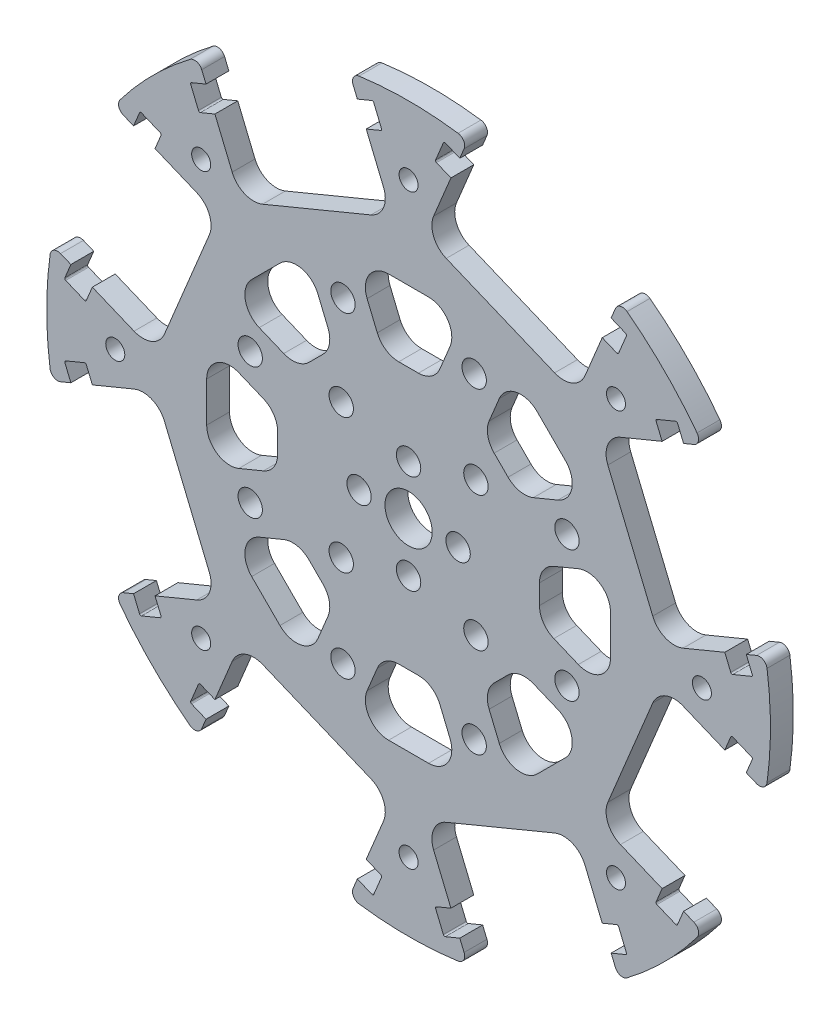
SolidWorks part; units mm, degrees
material "5052-H34"
ref_plane "正面" through (0, 0, 0) normal (0, 0, 1) x (1, 0, 0)
ref_plane "平面" through (0, 0, 0) normal (0, 1, 0) x (1, 0, 0)
ref_plane "右側面" through (0, 0, 0) normal (1, 0, 0) x (0, 0, -1)
sketch "ｽｹｯﾁ1" plane through (0, 0, 0) normal (0, 0, 1) x (1, 0, 0)
  circle A0 centre (0, 0) radius 47.5
  dimension "D1" = 95
extrude "ﾎﾞｽ - 押し出し1" add sketch "ｽｹｯﾁ1" along normal blind 3
sketch "ｽｹｯﾁ2" plane through (0, 0, 3) normal (0, 0, 1) x (1, 0, 0)
  line L0 (0, 0) -> (18.1775, 43.8843) construction
  line L1 (6.7246, 44.3257) -> (10.1592, 52.6175)
  line L2 (2.1228, 33.2161) -> (21.9862, 24.9884)
  line L3 (2.1228, 33.2161) -> (5.5574, 41.5079)
  line L4 (10.1592, 52.6175) -> (30.0226, 44.3898)
  line L5 (21.9862, 24.9884) -> (25.4208, 33.2802)
  line L6 (2.1228, 33.2161) -> (30.0226, 44.3898) construction
  line L7 (10.1592, 52.6175) -> (21.9862, 24.9884) construction
  line L8 (4.6459, 45.1867) -> (6.7246, 44.3257)
  line L9 (4.6459, 45.1867) -> (3.4787, 42.3689)
  line L10 (3.4787, 42.3689) -> (5.5574, 41.5079)
  line L11 (28.6667, 35.237) -> (27.4995, 32.4191)
  line L12 (4.6459, 45.1867) -> (27.4995, 32.4191) construction
  line L13 (3.4787, 42.3689) -> (28.6667, 35.237) construction
  line L14 (26.588, 36.098) -> (30.0226, 44.3898)
  line L15 (26.588, 36.098) -> (28.6667, 35.237)
  line L16 (0, 47.5) -> (0, 0) construction
  line L17 (25.4208, 33.2802) -> (27.4995, 32.4191)
  circle A0 centre (0, 0) radius 47.5 construction
  point P5 (16.0727, 38.8029)
  point P10 (16.0727, 38.8029)
  dimension "D1" = 42
  dimension "D2" = 21.5
  dimension "D3" = 21
  dimension "D4" = 3.05
  dimension "D5" = 26
  dimension "D6" = 22.5
extrude "ｶｯﾄ - 押し出し1" cut sketch "ｽｹｯﾁ2" against normal through all
sketch "ｽｹｯﾁ3" plane through (0, 0, 3) normal (0, 0, 1) x (1, 0, 0)
  line L1 (-8.8388, -8.8388) -> (8.8388, -8.8388) construction
  line L2 (-8.8388, -8.8388) -> (-8.8388, 8.8388) construction
  line L3 (-8.8388, 8.8388) -> (8.8388, 8.8388) construction
  line L4 (8.8388, -8.8388) -> (8.8388, 8.8388) construction
  line L5 (-8.8388, -8.8388) -> (8.8388, 8.8388) construction
  line L6 (-8.8388, 8.8388) -> (8.8388, -8.8388) construction
  circle A0 centre (0, 0) radius 3.1
  circle A1 centre (0, 0) radius 6.5 construction
  circle A2 centre (0, 6.5) radius 1.6
  circle A3 centre (6.5, 0) radius 1.6
  circle A4 centre (0, -6.5) radius 1.6
  circle A5 centre (-6.5, 0) radius 1.6
  circle A6 centre (0, 0) radius 12.5 construction
  circle A7 centre (8.8388, 8.8388) radius 1.6
  circle A8 centre (8.8388, -8.8388) radius 1.6
  circle A9 centre (-8.8388, -8.8388) radius 1.6
  circle A10 centre (-8.8388, 8.8388) radius 1.6
  dimension "D1" = 6.2
  dimension "D2" = 13
  dimension "D3" = 3.2
  dimension "D5" = 25
  dimension "D6" = 3.2
  dimension "D4" = 4
  dimension "D7" = 4
extrude "ｶｯﾄ - 押し出し2" cut sketch "ｽｹｯﾁ3" against normal through all and the other way through all
sketch "ｽｹｯﾁ4" plane through (0, 0, 3) normal (0, 0, 1) x (1, 0, 0)
  line L0 (0, 38.5) -> (0, 0) construction
  line L1 (8.6104, 20.7873) -> (0, 0) construction
  line L2 (0, 0) -> (27.2236, 27.2236) construction
  circle A0 centre (0, 0) radius 22.5 construction
  circle A1 centre (0, 0) radius 38.5 construction
  circle A2 centre (27.2236, 27.2236) radius 1.25
  circle A3 centre (8.6104, 20.7873) radius 1.6
  dimension "D1" = 45
  dimension "D2" = 77
  dimension "D4" = 2.5
  dimension "D6" = 3.2
  dimension "D3" = 22.5
  dimension "D5" = 45
extrude "ｶｯﾄ - 押し出し3" cut sketch "ｽｹｯﾁ4" against normal through all
sketch "ｽｹｯﾁ5" plane through (0, 0, 3) normal (0, 0, 1) x (1, 0, 0)
  line L0 (0, 0) -> (8.6104, 20.7873) construction
  line L2 (2.1228, 33.2161) -> (21.9862, 24.9884) construction
  line L3 (7.1883, 26.5) -> (-7.1883, 26.5)
  line L4 (3.3281, 17.1806) -> (7.1883, 26.5)
  line L5 (0, 47.5) -> (0, 0) construction
  line L6 (2.1228, 33.2161) -> (21.9862, 24.9884)
  line L9 (3.3281, 17.1806) -> (-3.3281, 17.1806)
  line L10 (-3.3281, 17.1806) -> (-7.1883, 26.5)
  circle A0 centre (0, 0) radius 17.5 construction
  arc A1 (7.7741, 46.8595) -> (27.6375, 38.6318) centre (0, 0) ccw construction
  dimension "D3" = 35
  dimension "D2" = 26.5
  dimension "D1" = 3.5
extrude "ｶｯﾄ - 押し出し4" cut sketch "ｽｹｯﾁ5" against normal through all and the other way through all contours L10 L9 L4 L3 region at (0, 22.4105, 3)
fillet "ﾌｨﾚｯﾄ1" radius 1 2 edges at (27.6375, 38.6318, 1.5) (7.7741, 46.8595, 1.5)
fillet "ﾌｨﾚｯﾄ2" radius 0.2 4 edges at (28.6667, 35.237, 1.5) (27.4995, 32.4191, 1.5) (4.6459, 45.1867, 1.5) (3.4787, 42.3689, 1.5)
fillet "ﾌｨﾚｯﾄ3" radius 3.05 2 edges at (21.9862, 24.9884, 1.5) (2.1228, 33.2161, 1.5)
fillet "ﾌｨﾚｯﾄ4" radius 3.05 4 edges at (7.1883, 26.5, 1.5) (-7.1883, 26.5, 1.5) (3.3281, 17.1806, 1.5) (-3.3281, 17.1806, 1.5)
ref_axis "軸1" through (0, 0, 0) along (0, 0, 1)
pattern_circular "円形ﾊﾟﾀｰﾝ1" count 8 over 360 about axis through (0, 0, 0) along (0, 0, 1) of "ｶｯﾄ - 押し出し1", "ﾌｨﾚｯﾄ1", "ｶｯﾄ - 押し出し4", "ｶｯﾄ - 押し出し3", "ﾌｨﾚｯﾄ2", "ﾌｨﾚｯﾄ3", "ﾌｨﾚｯﾄ4"
